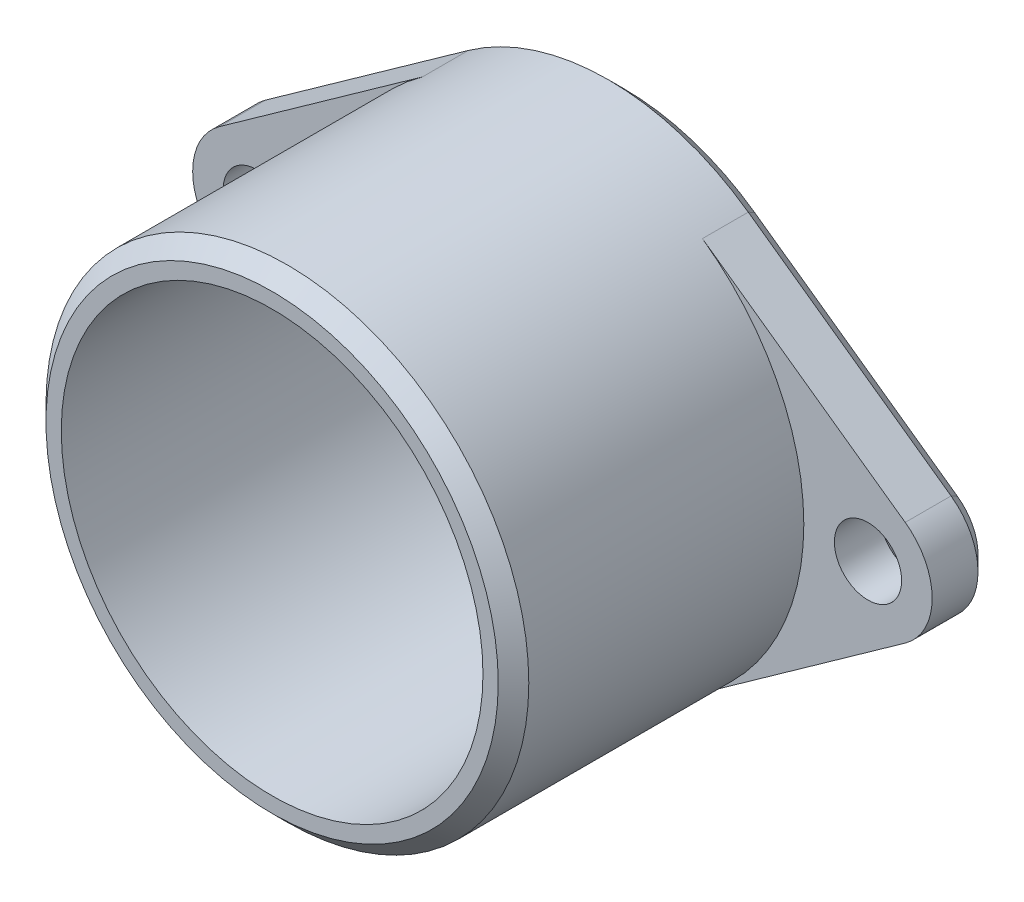
SolidWorks part; units mm, degrees
material "ABS"
ref_plane "Front" through (0, 0, 0) normal (0, 0, 1) x (1, 0, 0)
ref_plane "Top" through (0, 0, 0) normal (0, 1, 0) x (1, 0, 0)
ref_plane "Right" through (0, 0, 0) normal (1, 0, 0) x (0, 0, -1)
sketch "Эскиз2" plane through (0, 0, 0) normal (0, 0, 1) x (1, 0, 0)
  line L0 (4.582, 6.4355) -> (11.218, 1.7107)
  line L1 (11.218, -1.7107) -> (4.582, -6.4355)
  line L2 (-10, 0) -> (10, 0) construction
  line L3 (-4.582, -6.4355) -> (-11.218, -1.7107)
  line L4 (-4.582, 6.4355) -> (-11.218, 1.7107)
  line L5 (0, -7.9) -> (0, 7.9) construction
  arc A1 (11.218, 1.7107) -> (11.218, -1.7107) centre (10, 0) cw
  circle A2 centre (10, 0) radius 1.1
  arc A3 (4.582, -6.4355) -> (-4.582, -6.4355) centre (0, 0) cw
  circle A4 centre (-10, 0) radius 1.1
  arc A5 (-11.218, -1.7107) -> (-11.218, 1.7107) centre (-10, 0) cw
  arc A6 (4.582, 6.4355) -> (-4.582, 6.4355) centre (0, 0) ccw
  circle A7 centre (0, 4.5) radius 1
  circle A9 centre (0, -4.5) radius 1
  circle A10 centre (0, 0) radius 1.7
  point P12 (0, 0)
  dimension "D1" = 2.2
  dimension "D2" = 2.1
  dimension "D4" = 15.8
  dimension "D5" = 2
  dimension "D7" = 3.4
  dimension "D3" = 20
  dimension "D6" = 9
extrude "Основание" add sketch "Эскиз2" along normal blind 2
sketch "Эскиз3" plane through (0, 0, 2) normal (0, 0, 1) x (1, 0, 0)
  circle A0 centre (0, 0) radius 7.9
  arc A1 (-4.582, -6.4355) -> (4.582, -6.4355) centre (0, 0) ccw construction
extrude "Вытянуть-Тонкостенный1" add sketch "Эскиз3" along normal offset from surface (9.5 mm away) 11.5 thin up to face at (0, 0, 0) thin type one direction reverse wall 1
chamfer "Фаска1" distance 0.5 angle 45 14 edges at (-8.9, 0, 0) (1.7, 0, 0) (-1, -4.5, 0) (1, 4.5, 0) (11.1, 0, 0) (-7.9, 4.0731, 0) (-12.1, 0, 0) (-7.9, -4.0731, 0) (0, -7.9, 0) (7.9, -4.0731, 0) (12.1, 0, 0) (7.9, 4.0731, 0) (0, 7.9, 0) (7.9, 0, 11.5)
sketch "Эскиз4" plane through (0, 0, 2) normal (0, 0, 1) x (1, 0, 0)
  circle A0 centre (0, 0) radius 6.9
  circle A1 centre (0, 0) radius 6.9 construction
extrude "Вырез-Вытянуть1" cut sketch "Эскиз4" against normal blind 0.5
sketch "Эскиз5" plane through (0, 0, 1.5) normal (0, 0, 1) x (1, 0, 0)
  circle A0 centre (0, 0) radius 2.25
  dimension "D1" = 4.5
extrude "Вырез-Вытянуть2" cut sketch "Эскиз5" against normal blind 0.9
